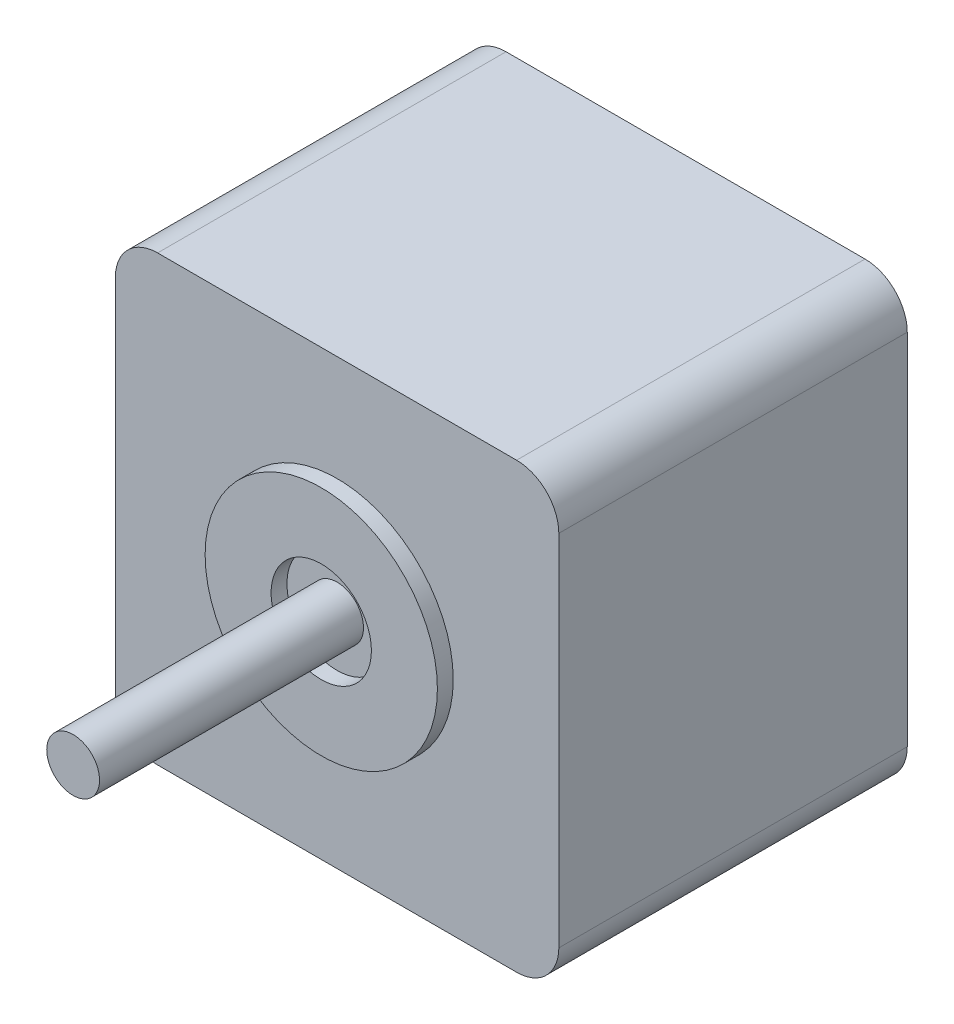
SolidWorks part; units mm, degrees
ref_plane "Alzado" through (0, 0, 0) normal (0, 0, 1) x (1, 0, 0)
ref_plane "Planta" through (0, 0, 0) normal (0, 1, 0) x (1, 0, 0)
ref_plane "Vista lateral" through (0, 0, 0) normal (1, 0, 0) x (0, 0, -1)
sketch "Croquis1" plane through (0, 0, 0) normal (0, 0, 1) x (1, 0, 0)
  line L1 (-21, -21) -> (21, -21)
  line L2 (-21, -21) -> (-21, 21)
  line L3 (-21, 21) -> (21, 21)
  line L4 (21, -21) -> (21, 21)
  line L5 (-21, -21) -> (21, 21) construction
  line L6 (-21, 21) -> (21, -21) construction
  point P0 (0, 0)
  dimension "D1" = 42
  dimension "D2" = 42
extrude "Saliente-Extruir1" add sketch "Croquis1" along normal blind 33
fillet "Redondeo1" radius 4 4 edges at (-21, -21, 16.5) (21, -21, 16.5) (21, 21, 16.5) (-21, 21, 16.5)
sketch "Croquis2" plane through (0, 0, 33) normal (0, 0, 1) x (1, 0, 0)
  circle A0 centre (0, 0) radius 11
  circle A1 centre (0, 0) radius 2.5
  circle A2 centre (0, 0) radius 4.75
  dimension "D1" = 22
  dimension "D2" = 5
  dimension "D3" = 9.5
extrude "Saliente-Extruir2" add sketch "Croquis2" along normal blind 1.5 contours A0 A2 region at (-10.6889, 0, 33)
extrude "Saliente-Extruir3" add sketch "Croquis2<4>" along normal blind 25 contours A1 region at (0, 0, 33)
sketch "Croquis2<4>" plane through (0, 0, 33) normal (0, 0, 1) x (1, 0, 0) same geometry as "Croquis2"
